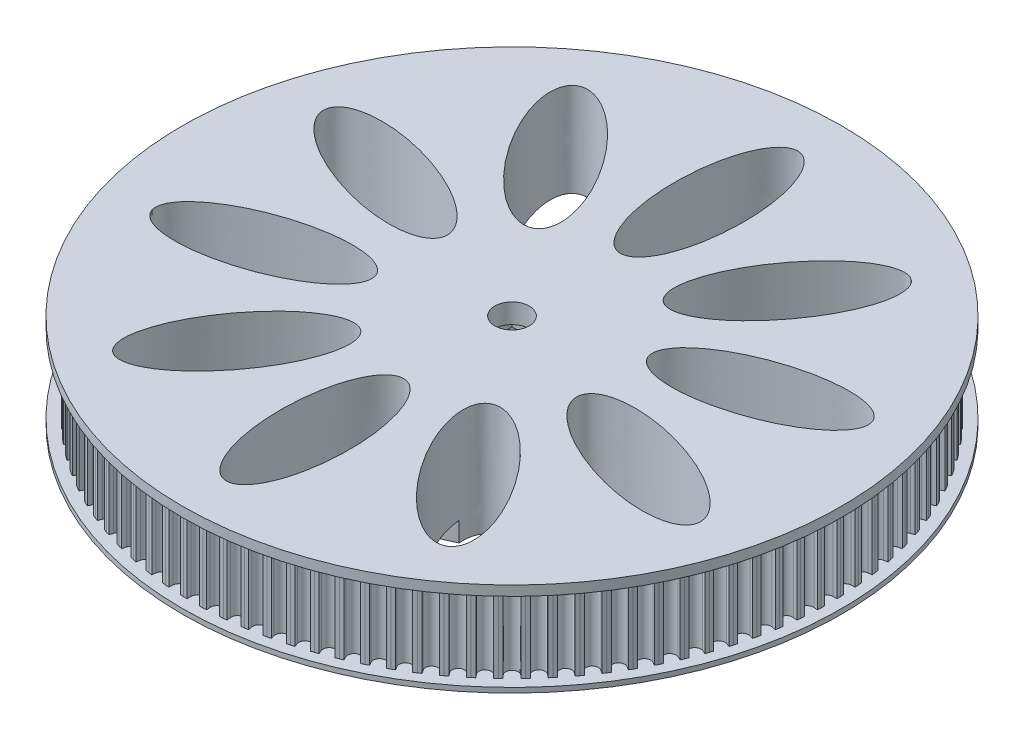
SolidWorks part; units mm, degrees
ref_plane "Front Plane" through (0, 0, 0) normal (0, 0, 1) x (1, 0, 0)
ref_plane "Top Plane" through (0, 0, 0) normal (0, 1, 0) x (1, 0, 0)
ref_plane "Right Plane" through (0, 0, 0) normal (1, 0, 0) x (0, 0, -1)
sketch "Sketch1" plane through (0, 0, 0) normal (0, 1, 0) x (1, 0, 0)
  circle A0 centre (0, 0) radius 33.4456
  circle A1 centre (0, 0) radius 8.55
  ellipse E0 centre (0, 20) end of major axis (0, 11) minor radius 3.5
  ellipse E1 centre (11.7557, 16.1803) end of major axis (6.4656, 8.8992) minor radius 3.5
  ellipse E2 centre (19.0211, 6.1803) end of major axis (27.5806, 8.9615) minor radius 3.5
  ellipse E3 centre (19.0211, -6.1803) end of major axis (10.4616, -3.3992) minor radius 3.5
  ellipse E4 centre (11.7557, -16.1803) end of major axis (17.0458, -23.4615) minor radius 3.5
  ellipse E5 centre (0, -20) end of major axis (0, -11) minor radius 3.5
  ellipse E6 centre (-11.7557, -16.1803) end of major axis (-6.4656, -8.8992) minor radius 3.5
  ellipse E7 centre (-19.0211, -6.1803) end of major axis (-27.5806, -8.9615) minor radius 3.5
  ellipse E8 centre (-19.0211, 6.1803) end of major axis (-27.5806, 8.9615) minor radius 3.5
  ellipse E9 centre (-11.7557, 16.1803) end of major axis (-17.0458, 23.4615) minor radius 3.5
  point P66 (0, 0)
  dimension "D1" = 66.8912
  dimension "D2" = 17.1
  dimension "D3" = 20
  dimension "D4" = 7
  dimension "D5" = 18
  dimension "D6" = 10
extrude "Boss-Extrude1" add sketch "Sketch1" along normal blind 11.5
sketch "Sketch2" plane through (0, 11.5, 0) normal (0, 1, 0) x (1, 0, 0)
  circle A0 centre (0, 0) radius 8.55
  circle A1 centre (0, 0) radius 8.55 construction
  circle A2 centre (0, 0) radius 1.75
  dimension "D1" = 3.5
extrude "Boss-Extrude2" add sketch "Sketch2" against normal blind 2
sketch "Sketch3" plane through (0, 9.5, 0) normal (0, -1, 0) x (-1, 0, 0)
  line L1 (6.0458, 6.0458) -> (-6.0458, 6.0458)
  line L2 (6.0458, 6.0458) -> (6.0458, -6.0458)
  line L3 (6.0458, -6.0458) -> (-6.0458, -6.0458)
  line L4 (-6.0458, 6.0458) -> (-6.0458, -6.0458)
  line L5 (6.0458, 6.0458) -> (-6.0458, -6.0458) construction
  line L6 (6.0458, -6.0458) -> (-6.0458, 6.0458) construction
  circle A0 centre (0, 0) radius 8.55 construction
  circle A1 centre (0, 0) radius 8.55 construction
  circle A2 centre (0, 0) radius 8.55
  point P0 (0, 0)
  circle M6 centre (0, 0) radius 8.55
extrude "Boss-Extrude3" add sketch "Sketch3" along normal blind 5 contours L3 M6 | L2 M6 | L4 M6 | L1 M6 region at (-7.0612, 9.5, 0) region at (0, 9.5, -7.0612) region at (7.0612, 9.5, 0) region at (0, 9.5, 7.0612)
sketch "Sketch4" plane through (0, 0, 0) normal (0, -1, 0) x (-1, 0, 0)
  circle A0 centre (0, 0) radius 12.55
  circle A1 centre (0, 0) radius 33.4456
  circle A2 centre (0, 0) radius 33.4456 construction
  arc A3 (-6.0458, 6.0458) -> (-6.0458, -6.0458) centre (0, 0) ccw construction
  dimension "D1" = 4
extrude "Cut-Extrude1" cut sketch "Sketch4" against normal blind 2 contours A1 | A0
sketch "Sketch5" plane through (0, 11.5, 0) normal (0, 1, 0) x (1, 0, 0)
  line L0 (0.63, 32.3456) -> (2, 32.3456)
  line L1 (-2, 32.3456) -> (-0.63, 32.3456)
  line L2 (-2, 32.3456) -> (-2, 35.3456)
  line L3 (-2, 35.3456) -> (2, 35.3456)
  line L4 (2, 32.3456) -> (2, 35.3456)
  line L5 (-0.63, 31.9456) -> (-0.63, 32.3456)
  line L6 (0.63, 31.9456) -> (0.63, 32.3456)
  arc A1 (-0.63, 31.9456) -> (0.63, 31.9456) centre (0, 31.9456) ccw
  point P12 (0, 35.3456)
  circle M9 centre (0, 0) radius 33.4456
  dimension "D2" = 1.26
  dimension "D3" = 4
  dimension "D1" = 31.9456
  dimension "D4" = 0.4
  dimension "D5" = 3
extrude "Cut-Extrude2" cut sketch "Sketch5" against normal blind 8 from offset 1 contours L5 A1 L6 L0 L4 L2 L1 M9 | L4 L3 L2 M9 region at (0, 11.5, -32.6791) region at (0, 11.5, -34.3855) offset against normal yes
pattern_circular "CirPattern1" count 104 over 360 about axis through (0, 9.5, 0) along (0, 1, 0) of "Cut-Extrude2" reverse direction yes
equation "\"pitch\"= 1.93"
equation "\"amount_of_teeth\"= 104"
equation "\"pitch_diameter\"= ( \"pitch\" * \"amount_of_teeth\" ) / pi"
equation "\"D1@Sketch1\"=\"pitch_diameter\"+3"
equation "\"D1@CirPattern1\"=\"amount_of_teeth\""
equation "\"D1@Sketch5\"=\"pitch_diameter\"/2"
